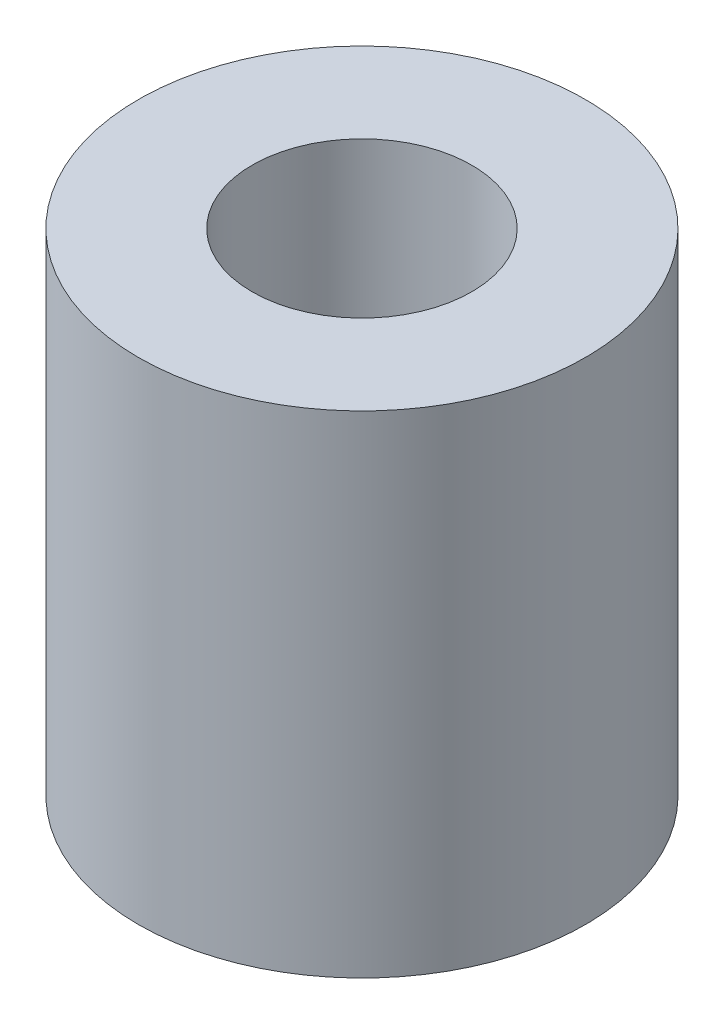
SolidWorks part; units mm, degrees
ref_plane "Front Plane" through (0, 0, 0) normal (0, 0, 1) x (1, 0, 0)
ref_plane "Top Plane" through (0, 0, 0) normal (0, 1, 0) x (1, 0, 0)
ref_plane "Right Plane" through (0, 0, 0) normal (1, 0, 0) x (0, 0, -1)
sketch "Sketch1" plane through (0, 0, 0) normal (0, 1, 0) x (1, 0, 0)
  circle A0 centre (0, 0) radius 10
  dimension "D1" = 20
extrude "Boss-Extrude1" add sketch "Sketch1" along normal blind 21.976
sketch "Sketch2" plane through (0, 21.976, 0) normal (0, 1, 0) x (1, 0, 0)
  circle A0 centre (0, 0) radius 4.9125
  point P0 (0, 0)
  dimension "D1" = 9.825
extrude "Cut-Extrude1" cut sketch "Sketch2" against normal through all contours A0
